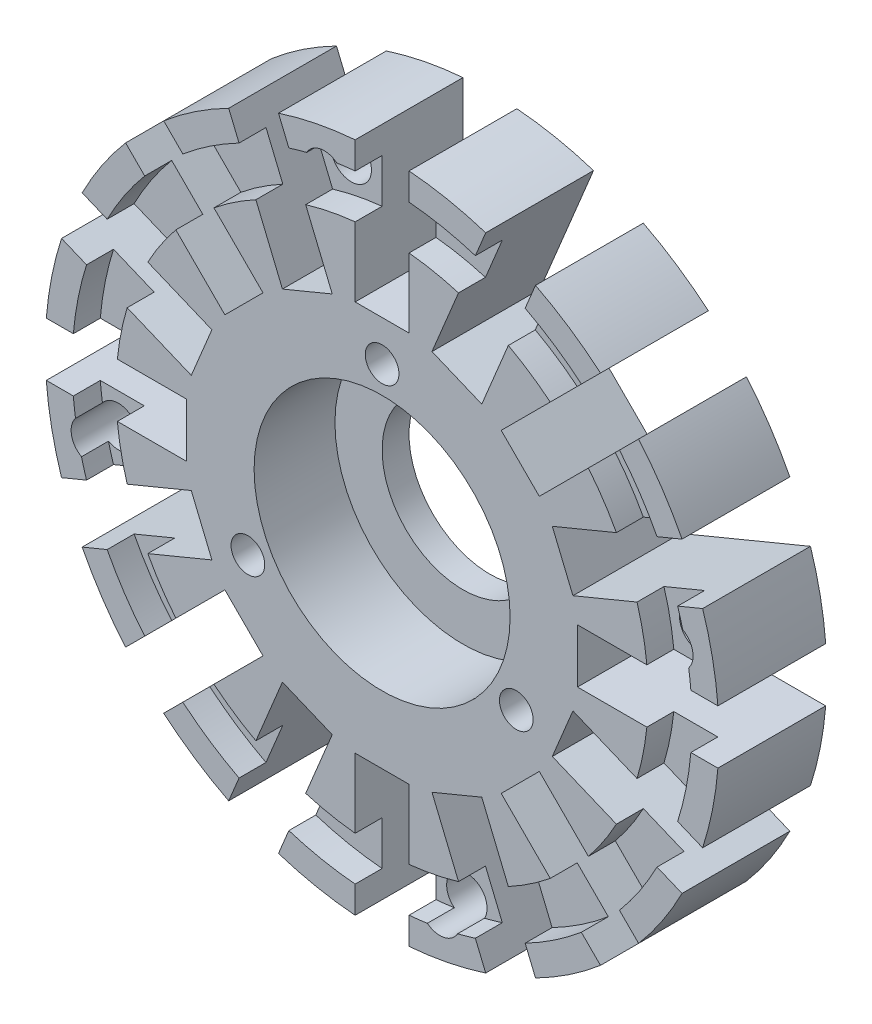
SolidWorks part; units mm, degrees
material "6061 Alloy"
ref_plane "Plano frontal" through (0, 0, 0) normal (0, 0, 1) x (1, 0, 0)
ref_plane "Plano superior" through (0, 0, 0) normal (0, 1, 0) x (1, 0, 0)
ref_plane "Plano direito" through (0, 0, 0) normal (1, 0, 0) x (0, 0, -1)
sketch "Esboço1" plane through (0, 0, 0) normal (0, 0, 1) x (1, 0, 0)
  circle A0 centre (0, 0) radius 25
extrude "Extrusão1" add sketch "Esboço1" against normal blind 8
sketch "Esboço2" plane through (0, 0, -8) normal (0, 0, -1) x (-1, 0, 0)
  line L1 (0, 14.5) -> (2, 14.5)
  line L2 (2, 14.5) -> (2, 29.5)
  line L3 (2, 29.5) -> (-2, 29.5)
  line L4 (-2, 29.5) -> (-2, 14.5)
  line L5 (-2, 14.5) -> (0, 14.5)
extrude "Extrusão2" add sketch "Esboço2" against normal through all separate body
ref_axis "Eixo1" through (0, 0, -23.3345) along (0, 0, 1)
pattern_circular "CirPattern1" count 16 over 360 about axis through (0, 0, -23.3345) along (0, 0, 1) of bodies 102
combine bodies "Combinar1" operation type subtract main body 101 bodies to subtract 103 102 117 116 115 114 113 112 111 110 109 108 107 106 105 104
sketch "Esboço5" plane through (0, 0, -8) normal (0, 0, -1) x (-1, 0, 0)
  circle A0 centre (0, 11.5) radius 1.25
  circle A1 centre (9.9593, -5.75) radius 1.25
  circle A2 centre (-9.9593, -5.75) radius 1.25
  circle A3 centre (0, 0) radius 6
  dimension "D1" = 12
extrude "Corte-extrusão2" cut sketch "Esboço5" against normal through all and the other way blind 10
sketch "Esboço8" plane through (0, 0, 0) normal (0, 0, 1) x (1, 0, 0)
  circle A1 centre (0, 0) radius 23
  circle A2 centre (0, 0) radius 19.75
extrude "Corte-extrusão4" cut sketch "Esboço8" against normal blind 2
sketch "Esboço9" plane through (0, 0, 0) normal (0, 0, 1) x (1, 0, 0)
  circle A0 centre (0, 0) radius 9.5
  dimension "D1" = 19
extrude "Corte-extrusão5" cut sketch "Esboço9" against normal blind 6
sketch "Esboço10" plane through (0, 0, -8) normal (0, 0, -1) x (-1, 0, 0)
  line L0 (-2, -14.5) -> (-2, -24.9199) construction
  circle A0 centre (-4.29, -21.5777) radius 1.5
  circle A1 centre (-21.5777, 4.29) radius 1.5
  circle A2 centre (4.29, 21.5777) radius 1.5
  circle A3 centre (21.5777, -4.29) radius 1.5
  point P15 (0, 0)
  dimension "D1" = 2.29
  dimension "D3" = 3
  dimension "D4" = 4
  dimension "D2" = 22
extrude "Corte-extrusão6" cut sketch "Esboço10" against normal through all
